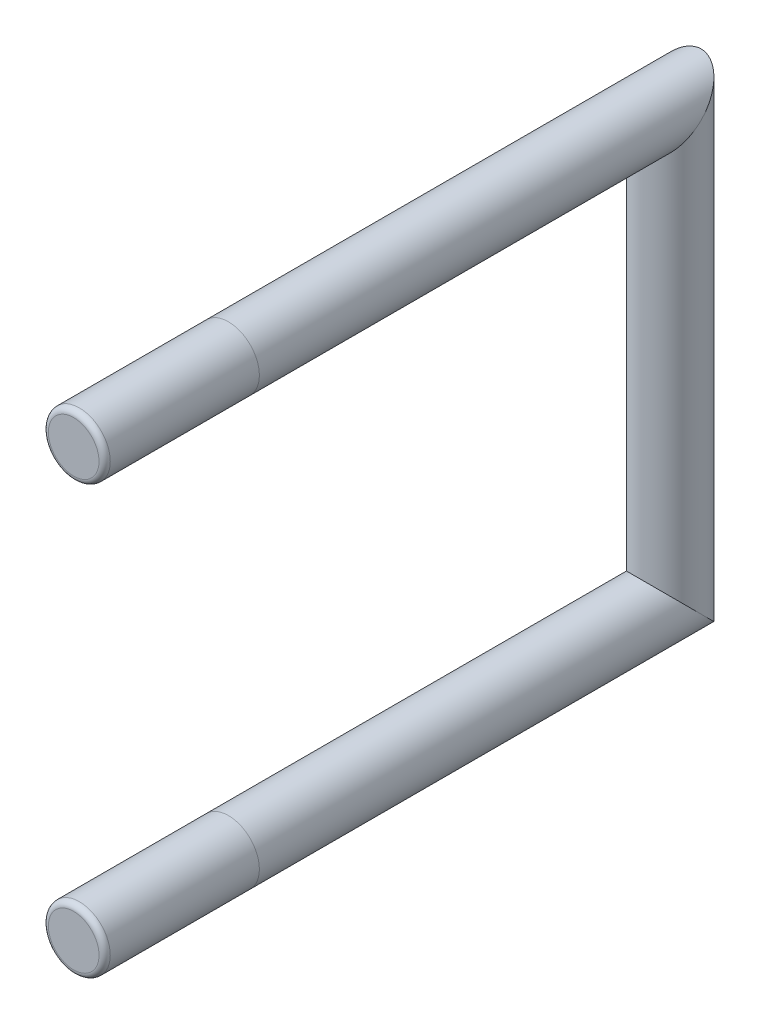
SolidWorks part; units mm, degrees
ref_plane "前视基准面" through (0, 0, 0) normal (0, 0, 1) x (1, 0, 0)
ref_plane "上视基准面" through (0, 0, 0) normal (0, 1, 0) x (1, 0, 0)
ref_plane "右视基准面" through (0, 0, 0) normal (1, 0, 0) x (0, 0, -1)
sketch "草图1" plane through (0, 0, 0) normal (0, 0, 1) x (1, 0, 0)
  circle A0 centre (0, 0) radius 11
  dimension "D1" = 22
extrude "拉伸1" add sketch "草图1" along normal blind 157
sketch "草图2" plane through (0, 0, 0) normal (0, 1, 0) x (1, 0, 0)
  circle A0 centre (0, 0) radius 11
  dimension "D1" = 22
extrude "拉伸2" add sketch "草图2" along normal blind 152
ref_axis "基准轴1" through (0, 171.9869, 0) along (0, -1, 0)
pattern_linear "阵列(线性)1" count 2 spacing 152 along (0, 1, 0) of "拉伸1"
chamfer "倒角3" distance 21.999 angle 45 2 edges at (0, 0, 0) (0, 152, 0)
sketch "草图3" plane through (0, 0, 157) normal (0, 0, 1) x (1, 0, 0)
  circle A0 centre (0, 152) radius 10.9995
  circle A1 centre (0, 0) radius 10.9995
  circle A2 centre (0, 152) radius 11 construction
  dimension "D1" = 21.999
extrude "拉伸3" add sketch "草图3" along normal blind 55
fillet "圆角1" radius 2 2 edges at (10.9995, 0, 212) (10.9995, 152, 212)
